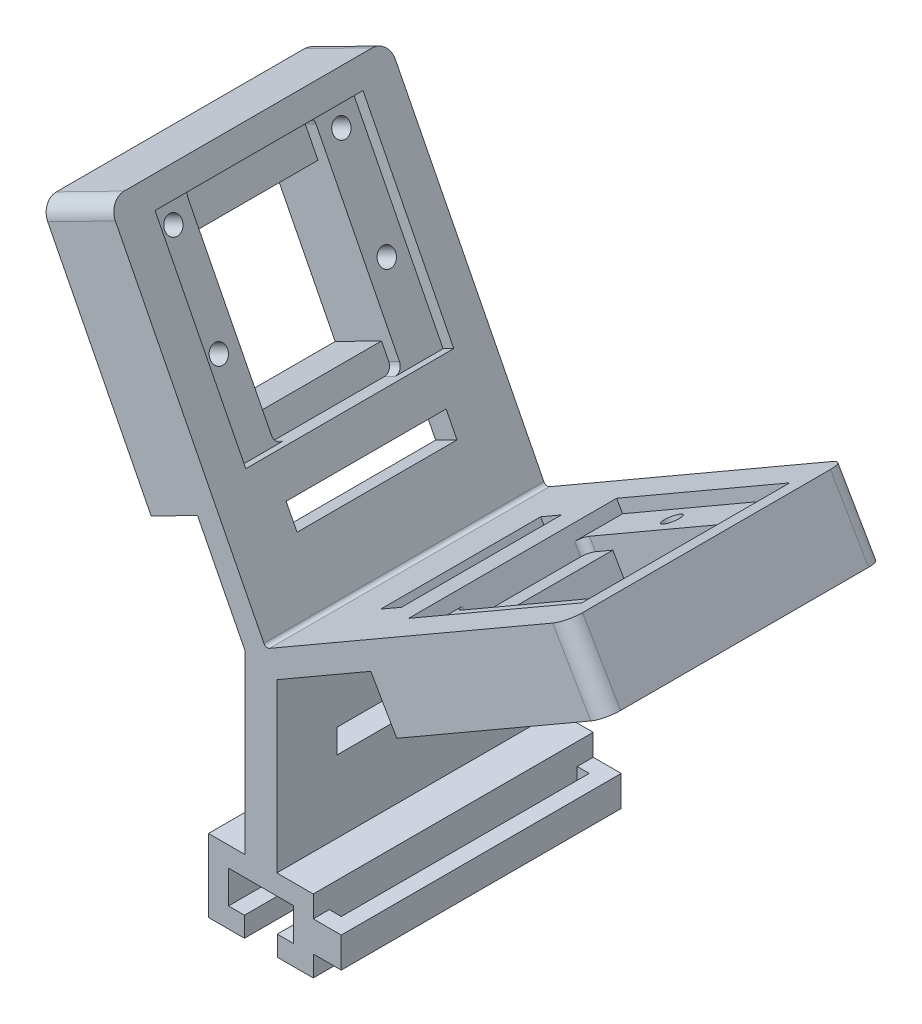
SolidWorks part; units mm, degrees
ref_plane "Front Plane" through (0, 0, 0) normal (0, 0, 1) x (1, 0, 0)
ref_plane "Top Plane" through (0, 0, 0) normal (0, 1, 0) x (1, 0, 0)
ref_plane "Right Plane" through (0, 0, 0) normal (1, 0, 0) x (0, 0, -1)
sketch "Sketch1" plane through (0, 0, 0) normal (0, 0, 1) x (1, 0, 0)
  line L0 (6.55, 4.55) -> (-6.55, 4.55)
  line L1 (4.05, 2.05) -> (-4.05, 2.05)
  line L2 (4.05, 2.05) -> (4.05, -2.05)
  line L3 (4.05, -2.05) -> (2.05, -2.05)
  line L4 (-4.05, 2.05) -> (-4.05, -2.05)
  line L5 (4.05, 2.05) -> (-4.05, -2.05) construction
  line L6 (4.05, -2.05) -> (-4.05, 2.05) construction
  line L7 (-6.55, 4.55) -> (-6.55, -4.55)
  line L8 (6.55, -4.55) -> (2.05, -4.55)
  line L9 (6.55, 4.55) -> (6.55, -4.55)
  line L10 (0, 0) -> (0, -4.55) construction
  line L11 (-2.05, -2.05) -> (-2.05, -4.55)
  line L12 (2.05, -2.05) -> (2.05, -4.55)
  line L13 (-2.05, -4.55) -> (-6.55, -4.55)
  line L14 (6.55, -4.55) -> (-6.55, -4.55) construction
  line L15 (-2.05, -2.05) -> (-4.05, -2.05)
  line L16 (4.05, -2.05) -> (-4.05, -2.05) construction
  line L17 (0, -2.05) -> (0, -4.55) construction
  point P0 (0, 0)
  dimension "D1" = 8.1
  dimension "D2" = 4.1
  dimension "D6" = 4.1
  dimension "D3" = 2.5
  dimension "D4" = 2.05
  dimension "D5" = 2.05
extrude "Boss-Extrude1" add sketch "Sketch1" along normal blind 35
sketch "Sketch2" plane through (0, 0, 35) normal (0, 0, 1) x (1, 0, 0)
  line L0 (0, 4.55) -> (0, 29.55) construction
  line L1 (6.55, 4.55) -> (-6.55, 4.55) construction
  line L2 (2, 4.55) -> (2, 25.4726)
  line L3 (-2, 4.55) -> (-2, 26.6712)
  line L4 (-2, 4.55) -> (2, 4.55)
  line L6 (0, 26.05) -> (38.9711, 48.55) construction
  line L7 (0, 26.05) -> (-20.4296, 66.1453) construction
  line L8 (2, 25.4726) -> (39.7211, 47.251)
  line L9 (0.6189, 28.1394) -> (38.2211, 49.849)
  line L10 (0.75, 24.751) -> (39.7211, 47.251) construction
  line L11 (-2, 26.6712) -> (-21.7661, 65.4643)
  line L12 (-1.3365, 25.369) -> (-21.7661, 65.4643) construction
  line L13 (-0.75, 27.349) -> (38.2211, 49.849) construction
  line L14 (0.6189, 28.1394) -> (-19.0931, 66.8263)
  line L15 (2, 4.55) -> (2, 29.55) construction
  line L17 (-2, 4.55) -> (-2, 29.55) construction
  line L18 (38.2211, 49.849) -> (39.7211, 47.251)
  line L19 (-21.7661, 65.4643) -> (-19.0931, 66.8263)
  dimension "D1" = 25
  dimension "D4" = 27
  dimension "D5" = 60
  dimension "D6" = 3.5
  dimension "D7" = 45
  dimension "D8" = 45
  dimension "D11" = 1.5
  dimension "D2" = 2
  dimension "D3" = 2
  dimension "D9" = 1.5
  dimension "D10" = 1.5
  dimension "D12" = 1.5
extrude "Boss-Extrude2" add sketch "Sketch2" against normal through all
fillet "Fillet1" radius 0.5 1 edges at (0.6189, 28.1394, 17.5)
sketch "Sketch3" plane through (-12.03, 20.8365, 0) normal (-0.5, 0.866, 0) x (0, 0, 1)
  line L0 (0, 58.025) -> (35, 58.025) construction
  line L1 (4.5, 55.025) -> (30.5, 55.025)
  line L2 (4.5, 55.025) -> (4.5, 30.025)
  line L3 (4.5, 30.025) -> (30.5, 30.025)
  line L4 (30.5, 55.025) -> (30.5, 30.025)
  line L5 (4.5, 55.025) -> (30.5, 30.025) construction
  line L6 (4.5, 30.025) -> (30.5, 55.025) construction
  line L7 (17.5, 42.525) -> (17.5, 58.025) construction
  point P0 (17.5, 42.525)
  dimension "D1" = 3
  dimension "D2" = 25
  dimension "D3" = 26
extrude "Cut-Extrude1" cut sketch "Sketch3" against normal blind 1.5
sketch "Sketch4" plane through (-11.28, 19.5375, 0) normal (-0.5, 0.866, 0) x (0, 0, 1)
  line L2 (25.5, 30.025) -> (25.5, 55.025)
  line L3 (25.5, 30.025) -> (25.5, 55.025)
  line L4 (9.5, 55.025) -> (25.5, 55.025)
  line L5 (9.5, 55.025) -> (9.5, 30.025)
  line L6 (9.5, 55.025) -> (9.5, 30.025)
  line L7 (9.5, 30.025) -> (26.4646, 30.025)
  line M4 (30.5, 55.025) -> (4.5, 55.025)
  line M6 (4.5, 30.025) -> (30.5, 30.025)
  dimension "D1" = 5
  dimension "D2" = 5
extrude "Cut-Extrude2" cut sketch "Sketch4" against normal blind 2 contours L6 L3 M4 M6 region at (25.5477, 40.8, 17.5)
fillet "Fillet3" radius 1 4 edges at (36.7481, 46.4005, 9.5) (36.7481, 46.4005, 25.5) (15.0974, 33.9005, 25.5) (15.0974, 33.9005, 9.5)
sketch "Sketch5" plane through (11.874, 6.0501, 0) normal (0.891, 0.454, 0) x (0, 0, -1)
  line L0 (-17.5, 68.2107) -> (-17.5, 52.7107) construction
  line L1 (-30.5, 65.2107) -> (-4.5, 65.2107)
  line L2 (-30.5, 65.2107) -> (-30.5, 40.2107)
  line L3 (-30.5, 40.2107) -> (-4.5, 40.2107)
  line L4 (-4.5, 65.2107) -> (-4.5, 40.2107)
  line L5 (-30.5, 65.2107) -> (-4.5, 40.2107) construction
  line L6 (-30.5, 40.2107) -> (-4.5, 65.2107) construction
  line L7 (0, 68.2107) -> (-35, 68.2107) construction
  point P0 (-17.5, 52.7107)
  dimension "D1" = 3
  dimension "D2" = 25
  dimension "D3" = 26
extrude "Cut-Extrude3" cut sketch "Sketch5" against normal blind 1.5
sketch "Sketch6" plane through (10.5374, 5.3691, 0) normal (0.891, 0.454, 0) x (0, 0, -1)
  line L2 (-25.5, 65.2107) -> (-25.5, 40.2107)
  line L3 (-25.5, 65.2107) -> (-25.5, 40.2107)
  line L4 (-9.5, 65.2107) -> (-25.5, 65.2107)
  line L5 (-9.5, 40.2107) -> (-9.5, 65.2107)
  line L6 (-9.5, 40.2107) -> (-9.5, 65.2107)
  line L7 (-25.5, 40.2107) -> (-9.5, 40.2107)
  dimension "D1" = 5
  dimension "D2" = 5
extrude "Cut-Extrude4" cut sketch "Sketch6" against normal blind 2
fillet "Fillet4" radius 1 4 edges at (-8.3861, 40.8566, 9.5) (-19.7359, 63.1318, 9.5) (-19.7359, 63.1318, 25.5) (-8.3861, 40.8566, 25.5)
sketch "Sketch8" plane through (-10.53, 18.2385, 0) normal (0.5, -0.866, 0) x (0, 0, -1)
  line L0 (-17.5, 24.025) -> (-17.5, 30.025) construction
  line L1 (-27.5, 25.525) -> (-7.5, 25.525)
  line L2 (-27.5, 25.525) -> (-27.5, 22.525)
  line L3 (-27.5, 22.525) -> (-7.5, 22.525)
  line L4 (-7.5, 25.525) -> (-7.5, 22.525)
  line L5 (-27.5, 25.525) -> (-7.5, 22.525) construction
  line L6 (-27.5, 22.525) -> (-7.5, 25.525) construction
  line L7 (-24.5, 30.025) -> (-10.5, 30.025) construction
  point P0 (-17.5, 24.025)
  dimension "D1" = 3
  dimension "D2" = 6
  dimension "D3" = 20
extrude "Cut-Extrude5" cut sketch "Sketch8" against normal blind 4
sketch "Sketch9" plane through (9.2009, 4.6881, 0) normal (-0.891, -0.454, 0) x (0, 0, 1)
  line L0 (17.5, 40.2107) -> (17.5, 34.2107) construction
  line L2 (10.5, 40.2107) -> (24.5, 40.2107) construction
  line L3 (7.5, 35.7107) -> (27.5, 35.7107)
  line L4 (7.5, 35.7107) -> (7.5, 32.7107)
  line L5 (7.5, 32.7107) -> (27.5, 32.7107)
  line L6 (27.5, 35.7107) -> (27.5, 32.7107)
  line L7 (7.5, 35.7107) -> (27.5, 32.7107) construction
  line L8 (7.5, 32.7107) -> (27.5, 35.7107) construction
  dimension "D1" = 6
  dimension "D2" = 20
  dimension "D3" = 3
extrude "Cut-Extrude6" cut sketch "Sketch9" against normal blind 4
sketch "Sketch10" plane through (-2, 0, 0) normal (-1, 0, 0) x (0, 0, 1)
  line L0 (17.5, 25.3744) -> (17.5, 4.75) construction
  line L4 (7.5, 16.5622) -> (27.5, 16.5622)
  line L5 (7.5, 16.5622) -> (7.5, 13.5622)
  line L6 (7.5, 13.5622) -> (27.5, 13.5622)
  line L7 (27.5, 16.5622) -> (27.5, 13.5622)
  line L8 (7.5, 16.5622) -> (27.5, 13.5622) construction
  line L9 (7.5, 13.5622) -> (27.5, 16.5622) construction
  point P6 (17.5, 15.0622)
  dimension "D1" = 20
  dimension "D2" = 3
extrude "Cut-Extrude7" cut sketch "Sketch10" against normal blind 4
sketch "Sketch11" plane through (-11.28, 19.5375, 0) normal (-0.5, 0.866, 0) x (0, 0, 1)
  line L0 (7, 40.025) -> (7, 52.525) construction
  line L1 (7, 52.525) -> (28, 52.525) construction
  line L2 (28, 52.525) -> (28, 40.025) construction
  line L3 (28, 40.025) -> (7, 40.025) construction
  line L4 (30.5, 55.025) -> (4.5, 55.025) construction
  line L5 (4.5, 55.025) -> (4.5, 30.025) construction
  circle A1 centre (28, 52.525) radius 1.1
  circle A3 centre (7, 52.525) radius 1.1
  circle A5 centre (28, 40.025) radius 1.1
  circle A7 centre (7, 40.025) radius 1.1
  dimension "D3" = 2.2
  dimension "D1" = 21
  dimension "D2" = 12.5
  dimension "D4" = 2.5
  dimension "D5" = 2.5
extrude "Cut-Extrude8" cut sketch "Sketch11" against normal blind 10
sketch "Sketch12" plane through (10.5374, 5.3691, 0) normal (0.891, 0.454, 0) x (0, 0, -1)
  line L0 (-28, 62.7107) -> (-28, 50.2107) construction
  line L2 (-28, 50.2107) -> (-7, 50.2107) construction
  line L5 (-7, 50.2107) -> (-7, 62.7107) construction
  line L6 (-7, 62.7107) -> (-28, 62.7107) construction
  line L7 (-4.5, 65.2107) -> (-30.5, 65.2107) construction
  line L8 (-30.5, 65.2107) -> (-30.5, 40.2107) construction
  circle A1 centre (-7, 62.7107) radius 1.1
  circle A3 centre (-28, 62.7107) radius 1.1
  circle A5 centre (-7, 50.2107) radius 1.1
  circle A7 centre (-28, 50.2107) radius 1.1
  dimension "D5" = 2.2
  dimension "D1" = 12.5
  dimension "D2" = 21
  dimension "D3" = 2.5
  dimension "D4" = 2.5
extrude "Cut-Extrude9" cut sketch "Sketch12" against normal blind 5
fillet "Fillet7" radius 2 4 edges at (38.9711, 48.55, 35) (38.9711, 48.55, 0) (-20.4296, 66.1453, 0) (-20.4296, 66.1453, 35)
sketch "Sketch14" plane through (6.55, 0, 0) normal (1, 0, 0) x (0, 0, -1)
  line L0 (-35, -0.1) -> (0, 0) construction
  line L3 (-35, 1.8508) -> (0, 1.8508)
  line L4 (-35, 1.8508) -> (-35, -1.9508)
  line L5 (-35, -1.9508) -> (0, -1.9508)
  line L6 (0, 1.8508) -> (0, -1.9508)
  line L7 (-35, 1.8508) -> (0, -1.9508) construction
  line L8 (-35, -1.9508) -> (0, 1.8508) construction
  point P5 (-17.5, -0.05)
extrude "Boss-Extrude3" add sketch "Sketch14" along normal blind 3.5 and the other way blind 1
sketch "Sketch15" plane through (0, 1.8508, 0) normal (0, 1, 0) x (1, 0, 0)
  line L6 (6.55, -35) -> (6.55, 0) construction
  line L7 (6.55, -33) -> (6.55, -2)
  line L9 (8.05, -33) -> (6.55, -33)
  line L10 (6.55, -2) -> (8.05, -2)
  line L11 (8.05, -2) -> (8.05, -33)
  line L12 (8.05, -33) -> (6.55, -33)
  line L13 (6.55, -2) -> (8.05, -2)
  line L14 (8.05, -2) -> (8.05, -33)
  dimension "D1" = 2
extrude "Cut-Extrude10" cut sketch "Sketch15" against normal blind 5
sketch "Sketch16" plane through (0, 4.55, 0) normal (0, 1, 0) x (1, 0, 0)
  line L1 (-30.4197, 7.2021) -> (26.8386, 7.2021)
  line L2 (-30.4197, 7.2021) -> (-30.4197, -38.2329)
  line L3 (-30.4197, -38.2329) -> (26.8386, -38.2329)
  line L4 (26.8386, 7.2021) -> (26.8386, -38.2329)
  line L5 (-30.4197, 7.2021) -> (26.8386, -38.2329) construction
  line L6 (-30.4197, -38.2329) -> (26.8386, 7.2021) construction
  point P0 (-1.7905, -15.5154)
extrude "Cut-Extrude11" [suppressed] cut sketch "Sketch16" against normal blind 10 and the other way blind 1
sketch "Sketch18" plane through (-10.53, 18.2385, 0) normal (0.5, -0.866, 0) x (0, 0, -1)
  line L0 (-35, 14.4684) -> (-35, 56.025) construction
  line L1 (0, 14.4684) -> (0, 56.025) construction
  line L2 (-2, 58.025) -> (-33, 58.025) construction
  line L3 (-35, 28.025) -> (-35, 56.025)
  line L4 (0, 28.025) -> (0, 56.025)
  line L5 (-2, 58.025) -> (-33, 58.025)
  line L6 (-25.5, 54.025) -> (-25.5, 31.025) construction
  line L7 (-9.5, 31.025) -> (-9.5, 54.025) construction
  line L9 (-25.5, 53.525) -> (-25.5, 33.525)
  line L10 (-9.5, 33.525) -> (-9.5, 53.525)
  line L11 (-35, 28.025) -> (0, 28.025)
  line L12 (-25.5, 53.525) -> (-9.5, 53.525)
  line L13 (-25.5, 33.525) -> (-9.5, 33.525)
  line L14 (-24.5, 30.025) -> (-10.5, 30.025) construction
  arc A0 (0, 56.025) -> (-2, 58.025) centre (-2, 56.025) ccw construction
  arc A1 (-33, 58.025) -> (-35, 56.025) centre (-33, 56.025) ccw construction
  arc A2 (0, 56.025) -> (-2, 58.025) centre (-2, 56.025) ccw
  arc A3 (-33, 58.025) -> (-35, 56.025) centre (-33, 56.025) ccw
  circle A4 centre (-7, 52.525) radius 1.1 construction
  circle A5 centre (-7, 40.025) radius 1.1 construction
  circle A6 centre (-28, 40.025) radius 1.1 construction
  circle A7 centre (-28, 52.525) radius 1.1 construction
  circle A8 centre (-7, 52.525) radius 1.1
  circle A9 centre (-7, 40.025) radius 1.1
  circle A10 centre (-28, 40.025) radius 1.1
  circle A11 centre (-28, 52.525) radius 1.1
  dimension "D1" = 2
  dimension "D2" = 4.5
  dimension "D3" = 3.5
extrude "Boss-Extrude4" add sketch "Sketch18" along normal blind 6.5
sketch "Sketch19" plane through (9.2009, 4.6881, 0) normal (-0.891, -0.454, 0) x (0, 0, 1)
  line L0 (25.5, 41.2107) -> (25.5, 64.2107) construction
  line L1 (9.5, 64.2107) -> (9.5, 41.2107) construction
  line L2 (25.5, 43.2107) -> (25.5, 60.7107)
  line L3 (9.5, 60.7107) -> (9.5, 43.2107)
  line L4 (33, 68.2107) -> (2, 68.2107)
  line L5 (0, 66.2107) -> (0, 24.6722)
  line L6 (0, 24.6722) -> (35, 24.6722)
  line L7 (35, 24.6722) -> (35, 66.2107)
  line L8 (33, 68.2107) -> (2, 68.2107)
  line L9 (0, 66.2107) -> (0, 37.7107)
  line L11 (35, 37.7107) -> (35, 66.2107)
  line L12 (9.5, 60.7107) -> (25.5, 60.7107)
  line L13 (9.5, 43.2107) -> (25.5, 43.2107)
  line L14 (24.5, 65.2107) -> (10.5, 65.2107) construction
  line L15 (10.5, 40.2107) -> (24.5, 40.2107) construction
  line L16 (0, 37.7107) -> (35, 37.7107)
  circle A0 centre (28, 62.7107) radius 1.1 construction
  circle A1 centre (28, 50.2107) radius 1.1 construction
  arc A2 (2, 68.2107) -> (0, 66.2107) centre (2, 66.2107) ccw
  arc A3 (35, 66.2107) -> (33, 68.2107) centre (33, 66.2107) ccw
  arc A4 (2, 68.2107) -> (0, 66.2107) centre (2, 66.2107) ccw
  arc A5 (35, 66.2107) -> (33, 68.2107) centre (33, 66.2107) ccw
  circle A6 centre (7, 50.2107) radius 1.1 construction
  circle A7 centre (7, 62.7107) radius 1.1 construction
  circle A8 centre (28, 50.2107) radius 1.1
  circle A9 centre (7, 50.2107) radius 1.1
  circle A10 centre (7, 62.7107) radius 1.1
  circle A11 centre (28, 62.7107) radius 1.1
  dimension "D2" = 4.5
  dimension "D3" = 3
  dimension "D4" = 2.5
  dimension "D1" = 0
extrude "Boss-Extrude5" add sketch "Sketch19" along normal blind 6.5
